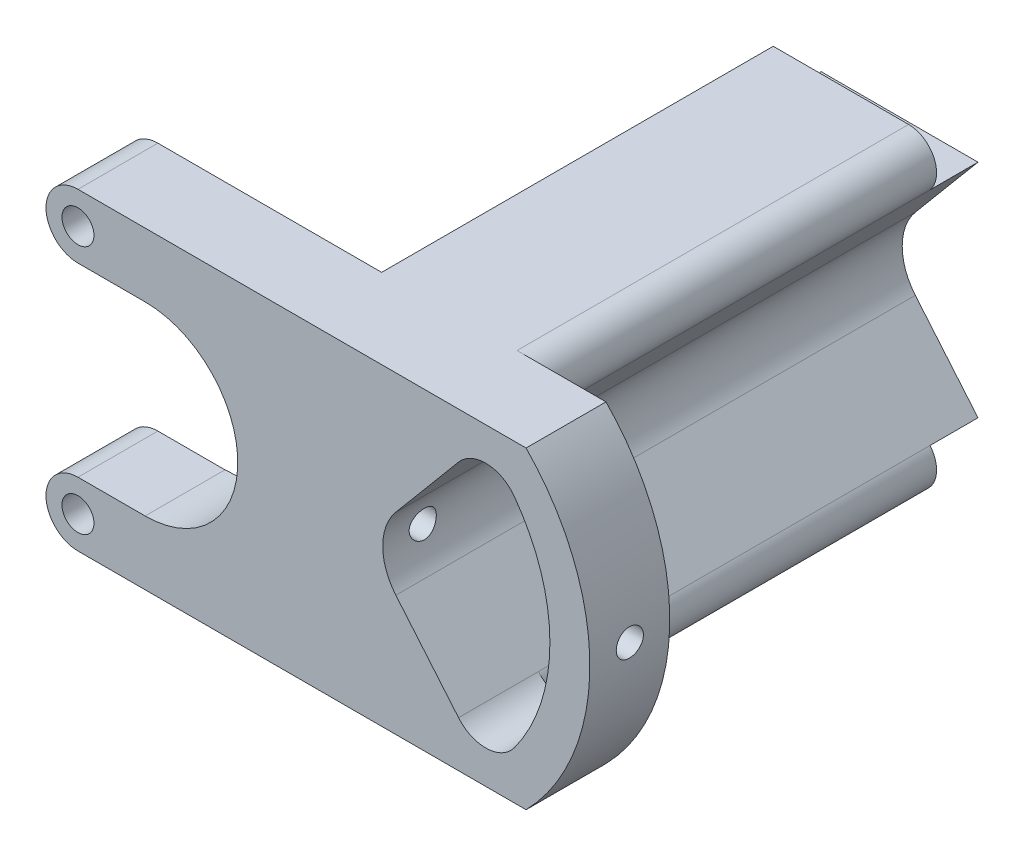
SolidWorks part; units mm, degrees
ref_plane "前视基准面" through (0, 0, 0) normal (0, 0, 1) x (1, 0, 0)
ref_plane "上视基准面" through (0, 0, 0) normal (0, 1, 0) x (1, 0, 0)
ref_plane "右视基准面" through (0, 0, 0) normal (1, 0, 0) x (0, 0, -1)
sketch "草图1" plane through (0, 0, 0) normal (0, 0, 1) x (1, 0, 0)
  line L0 (-314.3551, 0) -> (15403.4009, 0) construction
  line L1 (3.7755, 4.4995) -> (11.6217, 13.8502)
  line L2 (8.9406, 19.6) -> (-8, 19.6)
  line L3 (-8, 19.6) -> (-8, -19.6)
  line L4 (8.9406, -19.6) -> (-8, -19.6)
  line L5 (3.7755, -4.4995) -> (11.6217, -13.8502)
  line L6 (-8, 19.6) -> (-21.5, 19.6)
  line L7 (-52.8584, -11.6) -> (-16, -11.6) construction
  line L8 (-52.8584, -11.6) -> (-52.8584, 11.6) construction
  line L9 (-52.8584, 11.6) -> (-16, 11.6) construction
  line L10 (-16, -11.6) -> (-16, 11.6) construction
  line L11 (-52.8584, -11.6) -> (-16, 11.6) construction
  line L12 (-52.8584, 11.6) -> (-16, -11.6) construction
  line L13 (-36, -19.6) -> (-21.5, -19.6)
  line L14 (-21.5, -19.6) -> (-8, -19.6)
  line L15 (-36, 11.6) -> (-27.6, 11.6)
  line L16 (-16, -19.6) -> (-52.8584, -19.6) construction
  line L17 (-16, -19.6) -> (-16, 19.6) construction
  line L18 (-16, 19.6) -> (-52.8584, 19.6) construction
  line L19 (-52.8584, -19.6) -> (-52.8584, 19.6) construction
  line L20 (-16, -19.6) -> (-52.8584, 19.6) construction
  line L21 (-16, 19.6) -> (-52.8584, -19.6) construction
  line L22 (-31, -1000) -> (-31, 49000) construction
  line L23 (-36, 19.6) -> (-21.5, 19.6)
  line L24 (8.9406, 19.6) -> (20.0716, 19.6)
  line L25 (8.9406, -19.6) -> (20.0716, -19.6)
  line L26 (-27.6, -11.6) -> (-36, -11.6)
  circle A0 centre (0, 0) radius 23.0541 construction
  circle A1 centre (0, 0) radius 28.0541 construction
  circle A2 centre (-36, 15.6) radius 2
  circle A3 centre (-36, 15.6) radius 3.2 construction
  arc A4 (-36, 19.6) -> (-36, 11.6) centre (-36, 15.6) ccw
  arc A5 (3.7755, 4.4995) -> (3.7755, -4.4995) centre (9.1379, 0) ccw
  arc A6 (8.9406, -19.6) -> (11.6217, -13.8502) centre (8.9406, -16.1) ccw
  arc A7 (11.6217, 13.8502) -> (8.9406, 19.6) centre (8.9406, 16.1) ccw
  arc A8 (-36, -19.6) -> (-36, -11.6) centre (-36, -15.6) cw
  arc A9 (-27.6, -11.6) -> (-27.6, 11.6) centre (-27.6, 0) ccw
  circle A10 centre (-36, -15.6) radius 2
  circle A11 centre (-36, -15.6) radius 3.2 construction
  circle A12 centre (13.0541, 0) radius 10 construction
  arc A13 (20.0716, 19.6) -> (20.0716, -19.6) centre (0, 0) cw
  arc A14 (18.6012, 13.6194) -> (11.6217, 13.8502) centre (15.0209, 10.998) ccw
  arc A15 (18.6012, -13.6194) -> (11.6217, -13.8502) centre (15.0209, -10.998) cw
  arc A16 (18.6012, 13.6194) -> (18.6012, -13.6194) centre (0, 0) cw
  point P8 (-8, 0)
  point P9 (-34.4292, 0)
  point P18 (-34.4292, 0)
  point P38 (16.4464, -19.6)
  point P41 (16.4464, 19.6)
  dimension "D3" = 5
  dimension "D7" = 4
  dimension "D8" = 6.4
  dimension "D13" = 7
  dimension "D14" = 3.5
  dimension "D15" = 20
  dimension "D1" = 23.2
  dimension "D2" = 100
  dimension "D4" = 8
  dimension "D5" = 5.5
  dimension "D6" = 8
  dimension "D9" = 4
  dimension "D10" = 8
  dimension "D11" = 15
  dimension "D12" = 5
extrude "凸台-拉伸1" add sketch "草图1" along normal blind 10 contours L1 A7 L2 L3 L4 A6 L5 A5 | A9 L13 L14 L3 L6 L23 A2 A10 | A14 A16 A15 A6 L25 A13 L24 A7 region at (0.3153, 0, 0) region at (12.5079, 17.7635, 0) region at (-8.506, 0, 0)
extrude "凸台-拉伸2" add sketch "草图1<3>" against normal blind 15 contours L1 A7 L2 L3 L4 A6 L5 A5 region at (0.3153, 0, 0)
sketch "草图1<3>" plane through (0, 0, 0) normal (0, 0, 1) x (1, 0, 0) same geometry as "草图1"
extrude "凸台-拉伸3" add sketch "草图1<4>" against normal blind 40 from surface contours L1 A7 L2 L3 L4 A6 L5 A5 region at (0.3153, 0, 0) starting at face at (4.3376, 0, -15)
sketch "草图1<4>" plane through (0, 0, 0) normal (0, 0, 1) x (1, 0, 0) same geometry as "草图1"
sketch "草图2" plane through (0, 0, 0) normal (1, 0, 0) x (0, 0, -1)
  line L0 (-1000, 0) -> (49000, 0) construction
  line L2 (55, 19.6) -> (49, 19.6)
  line L3 (55, 19.6) -> (55, 13.8502)
  line L4 (55, 13.8502) -> (49, 13.8502)
  line L5 (49, 19.6) -> (49, 13.8502)
  line L6 (49, -19.6) -> (49, -13.8502)
  line L7 (55, -13.8502) -> (49, -13.8502)
  line L8 (55, -19.6) -> (55, -13.8502)
  line L9 (55, -19.6) -> (49, -19.6)
  circle A0 centre (-5, 0) radius 1.7
  dimension "D1" = 3.4
  dimension "D3" = 6
  dimension "D2" = 5
extrude "切除-拉伸1" cut sketch "草图2" against normal through all and the other way through all
